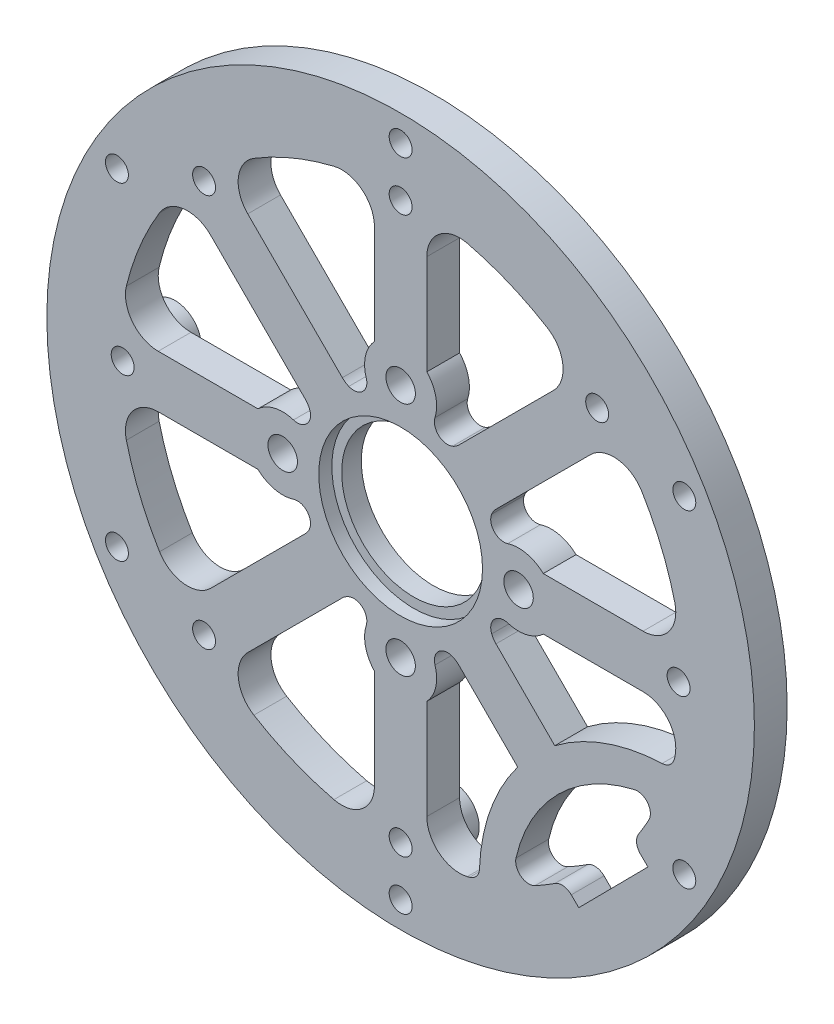
SolidWorks part; units mm, degrees
ref_plane "Front Plane" through (0, 0, 0) normal (0, 0, 1) x (1, 0, 0)
ref_plane "Top Plane" through (0, 0, 0) normal (0, 1, 0) x (1, 0, 0)
ref_plane "Right Plane" through (0, 0, 0) normal (1, 0, 0) x (0, 0, -1)
sketch "Sketch1" plane through (0, 0, 0) normal (0, 0, 1) x (1, 0, 0)
  circle A1 centre (0, 0) radius 54
  dimension "D1" = 108
extrude "Boss-Extrude1" add sketch "Sketch1" along normal blind 5
sketch "Sketch2" plane through (0, 0, 5) normal (0, 0, 1) x (1, 0, 0)
  line L0 (0, 36.927) -> (0, -25.0362) construction
  line L1 (-4, 14.4568) -> (-4, 42.8939)
  line L2 (4, 14.4568) -> (4, 42.8939)
  line L3 (7.3941, 13.051) -> (27.5021, 33.159)
  line L4 (13.051, 7.3941) -> (33.159, 27.5021)
  line L5 (14.4568, 4) -> (42.8939, 4)
  line L6 (14.4568, -4) -> (42.8939, -4)
  line L7 (13.051, -7.3941) -> (33.159, -27.5021)
  line L8 (7.3941, -13.051) -> (27.5021, -33.159)
  line L9 (4, -14.4568) -> (4, -42.8939)
  line L10 (-4, -14.4568) -> (-4, -42.8939)
  line L11 (-7.3941, -13.051) -> (-27.5021, -33.159)
  line L12 (-13.051, -7.3941) -> (-33.159, -27.5021)
  line L13 (-14.4568, -4) -> (-42.8939, -4)
  line L14 (-14.4568, 4) -> (-42.8939, 4)
  line L15 (-13.051, 7.3941) -> (-33.159, 27.5021)
  line L16 (-7.3941, 13.051) -> (-27.5021, 33.159)
  circle A0 centre (0, 0) radius 15
  circle A1 centre (0, 0) radius 43.08
  point P25 (0, 0)
  point P41 (0, 0)
  dimension "D1" = 30
  dimension "D2" = 86.16
  dimension "D3" = 8
  dimension "D4" = 8
extrude "Cut-Extrude4" cut sketch "Sketch2" against normal blind 10 contours L1 A1 L16 A0 | L3 A1 L2 A0 | L5 A1 L4 A0 | L7 A1 L6 A0 | L9 A1 L8 A0 | L11 A1 L10 A0 | L13 A1 L12 A0 | L15 A1 L14 A0 region at (-12.3019, 29.6993, 5) region at (12.3019, 29.6993, 5) region at (-29.6993, 12.3019, 5) region at (29.6993, 12.3019, 5) region at (-29.6993, -12.3019, 5) region at (29.6993, -12.3019, 5) region at (-12.3019, -29.6993, 5) region at (12.3019, -29.6993, 5)
sketch "Sketch3" plane through (0, 0, 5) normal (0, 0, 1) x (1, 0, 0)
  circle A0 centre (0, 0) radius 18 construction
  circle A1 centre (0, 18) radius 2.25
  circle A2 centre (18, 0) radius 2.25
  circle A3 centre (0, -18) radius 2.25
  circle A4 centre (-18, 0) radius 2.25
  point P14 (0, 0)
  dimension "D1" = 36
  dimension "D2" = 4.5
extrude "Cut-Extrude5" cut sketch "Sketch3" against normal blind 10
sketch "Sketch4" plane through (0, 0, 5) normal (0, 0, 1) x (1, 0, 0)
  circle A0 centre (0, 0) radius 50 construction
  circle A1 centre (0, 50) radius 1.75
  circle A2 centre (43.3013, 25) radius 1.75
  circle A3 centre (43.3013, -25) radius 1.75
  circle A4 centre (0, -50) radius 1.75
  circle A5 centre (-43.3013, -25) radius 1.75
  circle A6 centre (-43.3013, 25) radius 1.75
  point P18 (0, 0)
  dimension "D1" = 100
  dimension "D2" = 3.5
extrude "Cut-Extrude6" cut sketch "Sketch4" against normal blind 10
fillet "Fillet1" radius 5 16 edges at (-33.159, 27.5021, 2.5) (-42.8939, 4, 2.5) (-42.8939, -4, 2.5) (-33.159, -27.5021, 2.5) (-27.5021, -33.159, 2.5) (-4, -42.8939, 2.5) (4, -42.8939, 2.5) (27.5021, -33.159, 2.5) (33.159, -27.5021, 2.5) (42.8939, -4, 2.5) (42.8939, 4, 2.5) (33.159, 27.5021, 2.5) (27.5021, 33.159, 2.5) (4, 42.8939, 2.5) (-4, 42.8939, 2.5) (-27.5021, 33.159, 2.5)
fillet "Fillet3" radius 3 16 edges at (-14.4568, -4, 2.5) (-13.051, -7.3941, 2.5) (-7.3941, -13.051, 2.5) (-4, -14.4568, 2.5) (4, -14.4568, 2.5) (7.3941, -13.051, 2.5) (13.051, -7.3941, 2.5) (14.4568, -4, 2.5) (14.4568, 4, 2.5) (13.051, 7.3941, 2.5) (7.3941, 13.051, 2.5) (4, 14.4568, 2.5) (-4, 14.4568, 2.5) (-7.3941, 13.051, 2.5) (-13.051, 7.3941, 2.5) (-14.4568, 4, 2.5)
sketch "Sketch5" plane through (0, 0, 5) normal (0, 0, 1) x (1, 0, 0)
  circle A0 centre (0, 0) radius 11
  dimension "D1" = 22
extrude "Cut-Extrude7" cut sketch "Sketch5" against normal blind 10 contours A0
sketch "Sketch6" plane through (0, 0, 5) normal (0, 0, 1) x (1, 0, 0)
  circle A0 centre (0, 0) radius 45.5
  circle A1 centre (0, 0) radius 43.5
  dimension "D1" = 87
  dimension "D2" = 91
extrude "Boss-Extrude2" add sketch "Sketch6" against normal up to surface (5 mm away) up to face at (11, 0, 0)
sketch "Sketch7" plane through (0, 0, 5) normal (0, 0, 1) x (1, 0, 0)
  line L1 (-30, 30) -> (30, 30)
  line L2 (-30, 30) -> (-30, -30)
  line L3 (-30, -30) -> (30, -30)
  line L4 (30, 30) -> (30, -30)
  line L5 (-30, 30) -> (30, -30) construction
  line L6 (-30, -30) -> (30, 30) construction
  circle A0 centre (-30, 30) radius 1.75
  point P0 (0, 0)
  dimension "D2" = 3.5
  dimension "D1" = 60
extrude "Cut-Extrude8" cut sketch "Sketch7" against normal blind 7.5 contours L1 A0 L2 | L2 A0 L1 region at (-30.2476, 30.2476, 5) region at (-29.2573, 29.2573, 5)
pattern_circular "CirPattern1" count 8 over 360 about axis through (0, 0, -5) along (0, 0, 1) of "Cut-Extrude8"
sketch "Sketch8" plane through (0, 0, 5) normal (0, 0, 1) x (1, 0, 0)
  line L0 (0, 0) -> (-54, 0) construction
  circle A0 centre (0, 0) radius 54 construction
ref_plane "Plane1" through (0, -2.1651, 1.25) normal (0, 0.866, -0.5) x (-1, 0, 0)
sketch "Sketch9" plane through (0, 0, 0) normal (0, 0, -1) x (-1, 0, 0)
  line L0 (-26.0479, -20.391) -> (-36.7987, -22.3996)
  line L1 (-14.5545, -8.8976) -> (-28.9922, -23.3353) construction
  line L2 (-20.391, -26.0479) -> (-22.3996, -36.7987)
  line L3 (-8.8976, -14.5545) -> (-23.3353, -28.9922) construction
  arc A0 (-36.7987, -22.3996) -> (-22.3996, -36.7987) centre (0, 0) ccw
  arc A1 (-26.0479, -20.391) -> (-20.391, -26.0479) centre (0, 0) ccw
  dimension "D1" = 10
extrude "Cut-Extrude9" cut sketch "Sketch9" against normal blind 10
sketch "Sketch12" plane through (0, 0, 0) normal (0, 0, -1) x (-1, 0, 0)
  line L1 (-33.9221, -26.5552) -> (-26.9119, -33.6398)
  arc A0 (-29.2837, -31.5967) -> (-10.1817, -41.8595) centre (0, 0) ccw construction
ref_plane "Plane3" through (7.6042, -7.5244, -18.529) normal (0.3554, -0.3517, -0.866) x (-0.7034, -0.7108, 0)
sketch "Sketch13" plane through (7.6042, -7.5244, -18.529) normal (0.3554, -0.3517, -0.866) x (-0.7034, -0.7108, 0)
  line L0 (-4.9834, -37.0579) -> (4.9834, -37.0579) construction
  line L1 (-7.5, -32.0579) -> (7.5, -32.0579)
  line L2 (-7.5, -32.0579) -> (-7.5, -42.0579)
  line L3 (-7.5, -42.0579) -> (7.5, -42.0579)
  line L4 (7.5, -32.0579) -> (7.5, -42.0579)
  line L5 (-7.5, -32.0579) -> (7.5, -42.0579) construction
  line L6 (-7.5, -42.0579) -> (7.5, -32.0579) construction
  point P0 (0, -37.0579)
  dimension "D1" = 15
  dimension "D2" = 10
extrude "Cut-Extrude11" cut sketch "Sketch13" along normal through all and the other way through all
sketch "Sketch15" plane through (0, 0, 0) normal (0, 0, -1) x (-1, 0, 0)
  line L0 (0, 0) -> (0, -18) construction
  line L1 (0, 0) -> (-24.0416, -24.0416) construction
  line L2 (-30.4622, -30.4622) -> (-50.3192, -50.3192) construction
  arc A0 (-17.0562, -39.5597) -> (-39.5597, -17.0562) centre (-41.0122, -41.0122) ccw
  arc A1 (-12.0144, -41.3708) -> (-41.3708, -12.0144) centre (-41.0122, -41.0122) ccw
  arc A2 (-41.3708, -12.0144) -> (-39.5597, -17.0562) centre (0, 0) ccw
  arc A4 (-17.0562, -39.5597) -> (-12.0144, -41.3708) centre (0, 0) ccw
  dimension "D2" = 48
  dimension "D3" = 5
  dimension "D1" = 45
  dimension "D4" = 58
extrude "Boss-Extrude3" add sketch "Sketch15" against normal up to surface (5 mm away) up to face at (-41.189, 1.2374, 5)
fillet "Fillet4" radius 2 2 edges at (17.0562, -39.5597, 2.5) (39.5597, -17.0562, 2.5)
fillet "Fillet5" radius 2 2 edges at (41.3708, -12.0144, 2.5) (12.0144, -41.3708, 2.5)
fillet "Fillet6" radius 2 2 edges at (24.8797, -35.1694, 2.5) (35.4301, -24.507, 2.5)
sketch "Sketch16" plane through (0, 0, 0) normal (0, 0, -1) x (-1, 0, 0)
  circle A0 centre (-18, 0) radius 5.5
  circle A1 centre (-18, 0) radius 2.25
  circle A2 centre (0, 18) radius 2.25
  circle A3 centre (0, 18) radius 5.5
  circle A4 centre (18, 0) radius 2.25
  circle A5 centre (18, 0) radius 5.5
  circle A6 centre (0, -18) radius 2.25
  circle A7 centre (0, -18) radius 5.5
  point P16 (0, 0)
  dimension "D1" = 11
  dimension "D2" = 4
extrude "Boss-Extrude4" add sketch "Sketch16" against normal blind 5
fillet "Fillet7" radius 2 8 edges at (-14.8806, 4.5299, 2.5) (-14.8806, -4.5299, 2.5) (-4.5299, -14.8806, 2.5) (4.5299, -14.8806, 2.5) (14.8806, -4.5299, 2.5) (14.8806, 4.5299, 2.5) (4.5299, 14.8806, 2.5) (-4.5299, 14.8806, 2.5)
sketch "Sketch17" plane through (0, 0, 5) normal (0, 0, 1) x (1, 0, 0)
  circle A0 centre (0, 0) radius 12.5
  dimension "D1" = 25
extrude "Cut-Extrude12" cut sketch "Sketch17" against normal blind 2
sketch "Sketch18" plane through (0, 0, 0) normal (0, 0, -1) x (-1, 0, 0)
  circle A0 centre (0, -42.4264) radius 1.75 construction
  circle A1 centre (42.4264, 0) radius 1.75 construction
  circle A2 centre (0, 42.4264) radius 1.75 construction
  circle A3 centre (-42.4264, 0) radius 1.75 construction
  circle A4 centre (0, -42.4264) radius 1.75
  circle A5 centre (42.4264, 0) radius 1.75
  circle A6 centre (0, 42.4264) radius 1.75
  circle A7 centre (-42.4264, 0) radius 1.75
  circle A8 centre (0, 42.4264) radius 4
  dimension "D1" = 8
extrude "Boss-Extrude5" add sketch "Sketch18" along normal blind 3 contours A6 | A8 region at (0, 42.4264, 0)
pattern_circular "CirPattern2" count 4 over 360 about axis through (0, 0, -5) along (0, 0, 1) of "Boss-Extrude5"
